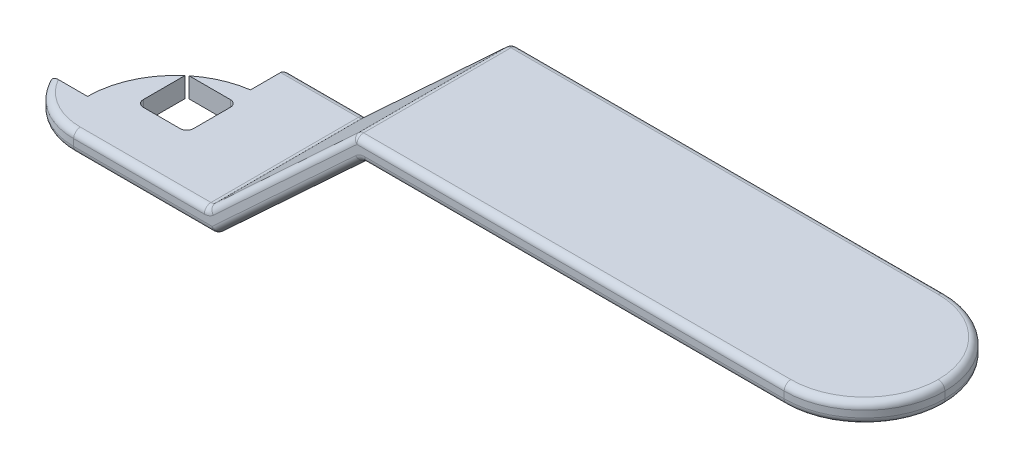
SolidWorks part; units mm, degrees
ref_plane "Front Plane" through (0, 0, 0) normal (0, 0, 1) x (1, 0, 0)
ref_plane "Top Plane" through (0, 0, 0) normal (0, 1, 0) x (1, 0, 0)
ref_plane "Right Plane" through (0, 0, 0) normal (1, 0, 0) x (0, 0, -1)
sketch "Sketch1" plane through (0, 0, 0) normal (0, 0, 1) x (1, 0, 0)
  line L0 (0, 0) -> (30, 0)
  line L1 (30, 0) -> (52, 20.3961)
  line L2 (52, 20.3961) -> (127, 20.3961)
  dimension "D1" = 30
  dimension "D2" = 30
  dimension "D3" = 75
  dimension "D4" = 22
extrude "Extrude-Thin1" add sketch "Sketch1" against normal blind 24 thin thin type one direction reverse wall 3
sketch "Sketch2" plane through (0, 3, 0) normal (0, 1, 0) x (1, 0, 0)
  line L0 (0, 24) -> (28.8233, 24) construction
  line L1 (0, 24) -> (0, 0) construction
  line L2 (0, 0) -> (0, 5.5)
  line L4 (0, 24) -> (0, 0)
  line L5 (0, 24) -> (28.8233, 24)
  line L7 (0, 5.5) -> (5.5, 5.5)
  line L8 (16.8233, 24) -> (16.8233, 18.5)
  line L9 (0, 0) -> (28.8233, 0) construction
  line L10 (28.8233, 24) -> (28.8233, 0) construction
  line L11 (17.5733, 8.25) -> (10.0733, 8.25)
  line L12 (17.5733, 8.25) -> (17.5733, 15.75)
  line L13 (17.5733, 15.75) -> (10.0733, 15.75)
  line L14 (10.0733, 8.25) -> (10.0733, 15.75)
  line L15 (17.5733, 8.25) -> (10.0733, 15.75) construction
  line L16 (17.5733, 15.75) -> (10.0733, 8.25) construction
  arc A1 (5.5, 5.5) -> (16.8233, 18.5) centre (18.6241, 5.5) cw
  point P10 (13.8233, 12)
  dimension "D1" = 5.5
  dimension "D2" = 12
  dimension "D3" = 5.5
  dimension "D4" = 7.5
  dimension "D5" = 11.25
  dimension "D6" = 5.5
  dimension "D7" = 8.25
extrude "Cut-Extrude1" cut sketch "Sketch2" against normal through all
fillet "Fillet1" radius 10 1 edges at (0, 1.5, 0)
fillet "Fillet2" radius 12 2 edges at (127, 21.8961, 0) (127, 21.8961, -24)
fillet "Fillet3" radius 1 23 edges at (3.6862, 0, -1.4853) (3.6862, 3, -1.4853) (123.4853, 23.3961, -20.4853) (123.4853, 23.3961, -3.5147) (123.4853, 20.3961, -20.4853) (123.4853, 20.3961, -3.5147) (39.8233, 13.198, -24) (22.8233, 3, -24) (23.4117, 0, -24) (41, 10.198, -24) (83.5, 20.3961, -24) (82.9117, 23.3961, -24) (41, 10.198, 0) (19.4651, 0, 0) (18.8768, 3, 0) (39.8233, 13.198, 0) (82.9117, 23.3961, 0) (83.5, 20.3961, 0) (52, 20.3961, -12) (30, 0, -12) (50.8233, 23.3961, -12) (28.8233, 3, -12) (16.8233, 1.5, -24)
fillet "Fillet4" radius 1 3 edges at (17.5733, 1.5, -8.25) (10.0733, 1.5, -8.25) (17.5733, 1.5, -15.75)
